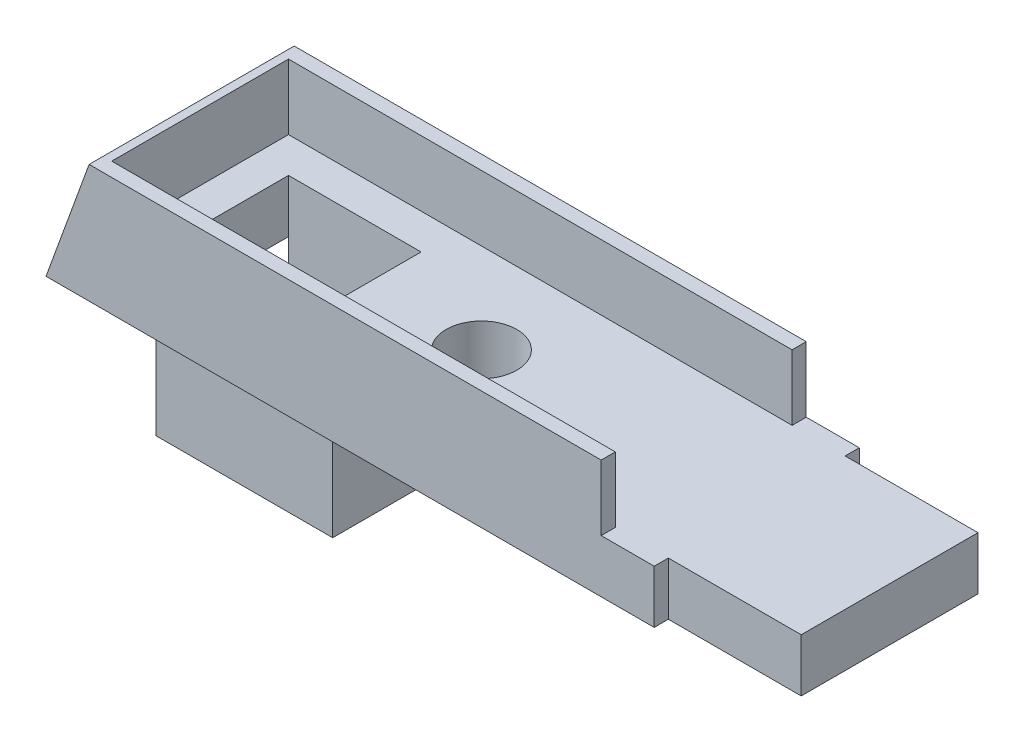
SolidWorks part; units mm, degrees
ref_plane "前视基准面" through (0, 0, 0) normal (0, 0, 1) x (1, 0, 0)
ref_plane "上视基准面" through (0, 0, 0) normal (0, 1, 0) x (1, 0, 0)
ref_plane "右视基准面" through (0, 0, 0) normal (1, 0, 0) x (0, 0, -1)
sketch "草图1" plane through (0, 0, 0) normal (0, 1, 0) x (1, 0, 0)
  line L0 (-13.0089, -6.3971) -> (-13.0089, -12.3971)
  line L1 (-14.0089, -4.3971) -> (-4.0242, -4.3971) construction
  line L2 (-14.0089, -4.3971) -> (-14.0089, -14.3971) construction
  line L3 (-14.0089, -14.3971) -> (-4.0242, -14.3971) construction
  line L4 (23.9911, -4.3971) -> (23.9911, -14.3971)
  line L5 (-13.0089, -12.3971) -> (-5.5089, -12.3971)
  line L6 (-5.5089, -12.3971) -> (-5.5089, -6.3971)
  line L7 (-5.5089, -6.3971) -> (-13.0089, -6.3971)
  line L9 (-53.0418, -9.3971) -> (30.158, -9.3971) construction
  line L13 (3.9758, -4.3971) -> (23.9911, -4.3971) construction
  line L17 (3.9758, -14.3971) -> (23.9911, -14.3971) construction
  line L18 (-4.0242, -3.5971) -> (-16.0089, -3.5971)
  line L19 (-16.0089, -3.5971) -> (-16.0089, -15.1971)
  line L20 (-16.0089, -15.1971) -> (-4.0242, -15.1971)
  line L21 (2.9758, -3.5971) -> (16.4758, -3.5971)
  line L22 (16.4758, -3.5971) -> (16.4758, -4.3971)
  line L23 (16.4758, -15.1971) -> (16.4758, -14.3971)
  line L24 (2.9758, -15.1971) -> (16.4758, -15.1971)
  line L25 (16.4758, -4.3971) -> (23.9911, -4.3971)
  line L26 (23.9911, -14.3971) -> (16.4758, -14.3971)
  line L27 (-4.0242, -15.1971) -> (2.9758, -15.1971)
  line L28 (-4.0242, -3.5971) -> (2.9758, -3.5971)
  point P12 (23.9911, -9.3971)
  dimension "D1" = 38
  dimension "D2" = 10
  dimension "D3" = 6
  dimension "D4" = 2
  dimension "D5" = 7.5
  dimension "D7" = 1
  dimension "D10" = 0.8
  dimension "D11" = 2
  dimension "D12" = 0.8
  dimension "D14" = 12.5
extrude "凸台-拉伸1" add sketch "草图1" along normal blind 3
sketch "草图2" plane through (0, 0, 0) normal (0, -1, 0) x (1, 0, 0)
  line L12 (-13.0089, 12.3971) -> (-13.0089, 13.8971)
  line L13 (-13.0089, 13.8971) -> (-3.0089, 13.8971)
  line L14 (-3.0089, 13.8971) -> (-3.0089, 4.8971)
  line L15 (-3.0089, 4.8971) -> (-13.0089, 4.8971)
  line L16 (-13.0089, 4.8971) -> (-13.0089, 6.3971)
  line L17 (-13.0089, 6.3971) -> (-13.0089, 12.3971) construction
  line L18 (-5.5089, 9.3971) -> (-6.8487, 9.3971) construction
  line L19 (-13.0089, 12.3971) -> (-5.5089, 12.3971)
  line L21 (-13.0089, 6.3971) -> (-5.5089, 6.3971)
  line L22 (-5.5089, 12.3971) -> (-5.5089, 6.3971)
  dimension "D1" = 1.5
  dimension "D2" = 2.5
extrude "凸台-拉伸2" add sketch "草图2" along normal blind 6
sketch "草图3" plane through (0, 3, 0) normal (0, 1, 0) x (1, 0, 0)
  line L0 (-14.0089, -9.4845) -> (-14.0089, -12.8636) construction
  line L1 (-17.6334, -9.4845) -> (28.8033, -9.4845) construction
  line L3 (-13.0089, -6.3971) -> (-13.0089, -12.3971) construction
  circle A0 centre (0.9911, -9.4845) radius 2
  dimension "D1" = 4
  dimension "D2" = 15
  dimension "D3" = 1
extrude "切除-拉伸1" cut sketch "草图3" against normal through all
sketch "草图4" plane through (0, 3, 0) normal (0, 1, 0) x (1, 0, 0)
  line L0 (-16.0089, -3.5971) -> (13.4758, -3.5971)
  line L1 (16.4758, -3.5971) -> (16.4758, -4.3971) construction
  line L2 (13.4758, -4.3971) -> (-15.0089, -4.3971)
  line L3 (-16.0089, -3.5971) -> (-16.0089, -15.1971)
  line L4 (-16.0089, -15.1971) -> (13.4758, -15.1971)
  line L5 (16.4758, -15.1971) -> (16.4758, -14.3971) construction
  line L6 (13.4758, -14.3971) -> (-15.0089, -14.3971)
  line L7 (-15.0089, -14.3971) -> (-15.0089, -4.3971)
  line L8 (13.4758, -14.3971) -> (13.4758, -15.1971)
  line L9 (13.4758, -15.1971) -> (16.4758, -15.1971) construction
  line L10 (16.4758, -14.3971) -> (13.4758, -14.3971) construction
  line L11 (13.4758, -3.5971) -> (13.4758, -4.3971)
  line L12 (13.4758, -3.5971) -> (16.4758, -3.5971) construction
  line L13 (16.4758, -4.3971) -> (13.4758, -4.3971) construction
  dimension "D1" = 1
  dimension "D2" = 3
extrude "凸台-拉伸3" add sketch "草图4" along normal blind 3.7
sketch "草图5" plane through (0, 6.7, 0) normal (0, 1, 0) x (1, 0, 0)
  line L0 (-16.0089, -3.5971) -> (-16.0089, -15.1971)
  line L1 (-16.0089, -15.1971) -> (-5.5089, -15.1971)
  line L2 (-16.0089, -15.1971) -> (13.4758, -15.1971) construction
  line L3 (-16.0089, -3.5971) -> (-5.5089, -3.5971)
  line L4 (13.4758, -3.5971) -> (-16.0089, -3.5971) construction
  line L5 (-5.5089, -3.5971) -> (-5.5089, -10.0171)
  line L6 (-8.2089, -10.0171) -> (-8.2089, -12.5171)
  line L7 (-8.2089, -12.5171) -> (-5.5089, -12.5171)
  line L9 (-5.5089, -10.0171) -> (-8.2089, -10.0171)
  line L10 (-5.5089, -12.5171) -> (-5.5089, -15.1971)
  dimension "D1" = 7.8
  dimension "D2" = 2.68
  dimension "D3" = 2.5
  dimension "D4" = 2.7
sketch "草图6" plane through (0, 3, 0) normal (0, 1, 0) x (1, 0, 0)
  line L0 (-16.0089, -3.5971) -> (-16.0089, -15.1971) construction
  line L2 (-17.6881, -9.3971) -> (25.119, -9.3971) construction
  point P0 (-16.0089, -9.3971)
sketch "草图7" plane through (0, 0, 15.1971) normal (0, 0, 1) x (1, 0, 0)
  line L0 (-16.0089, 0) -> (-16.0089, 6.7)
  line L1 (-16.0089, 6.7) -> (-18.4475, 0)
  line L3 (-18.4475, 0) -> (-16.0089, 0)
  dimension "D1" = 20
extrude "凸台-拉伸4" add sketch "草图7" against normal up to surface (11.6 mm away) up to face at (4.6476, 3.2333, 3.5971)
sketch "草图8" plane through (0, 0, 15.1971) normal (0, 0, 1) x (1, 0, 0)
  line L0 (-16.0089, 6.7) -> (-18.4475, 0)
  line L1 (-18.4475, 0) -> (-17.9261, 0)
  line L2 (-18.4475, 0) -> (16.4758, 0) construction
  line L3 (-17.9261, 0) -> (-15.4875, 6.7)
  line L4 (-16.0089, 6.7) -> (-5.5089, 6.7) construction
  line L5 (-15.4875, 6.7) -> (-16.0089, 6.7)
  dimension "D1" = 0.49
extrude "切除-拉伸2" cut sketch "草图8" against normal blind 12
